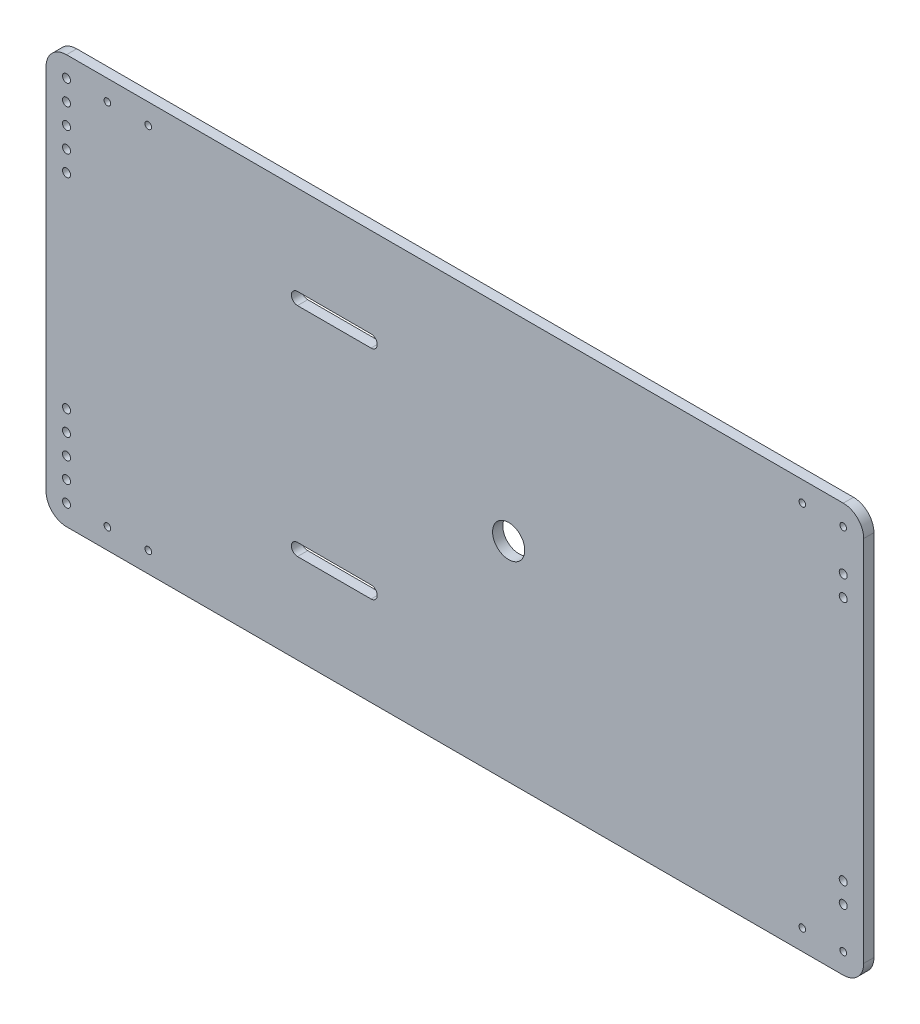
SolidWorks part; units mm, degrees
material "PC High Viscosity"
ref_plane "Front Plane" through (0, 0, 0) normal (0, 0, 1) x (1, 0, 0)
ref_plane "Top Plane" through (0, 0, 0) normal (0, 1, 0) x (1, 0, 0)
ref_plane "Right Plane" through (0, 0, 0) normal (1, 0, 0) x (0, 0, -1)
sketch "Sketch1" plane through (0, 0, 0) normal (0, 0, 1) x (1, 0, 0)
  line L1 (12.7, 0) -> (495.3, 0)
  line L2 (0, 12.7) -> (0, 241.3)
  line L3 (12.7, 254) -> (495.3, 254)
  line L4 (508, 12.7) -> (508, 241.3)
  arc A0 (495.3, 254) -> (508, 241.3) centre (495.3, 241.3) cw
  arc A1 (495.3, 0) -> (508, 12.7) centre (495.3, 12.7) ccw
  arc A2 (12.7, 0) -> (0, 12.7) centre (12.7, 12.7) cw
  arc A3 (0, 241.3) -> (12.7, 254) centre (12.7, 241.3) cw
  point P7 (508, 254)
  point P10 (508, 0)
  point P13 (0, 0)
  point P16 (0, 254)
  dimension "D3" = 12.7
  dimension "D1" = 508
  dimension "D2" = 254
extrude "Boss-Extrude1" add sketch "Sketch1" along normal blind 6.35
sketch "Sketch2" plane through (0, 0, 6.35) normal (0, 0, 1) x (1, 0, 0)
  line L10 (495.3, 254) -> (12.7, 254) construction
  line L11 (0, 241.3) -> (0, 12.7) construction
  line L12 (-20.2403, 127) -> (522.5431, 127) construction
  circle A6 centre (12.7, 190.5) radius 2.5
  circle A7 centre (12.7, 203.2) radius 2.5
  circle A8 centre (12.7, 215.9) radius 2.5
  circle A9 centre (12.7, 228.6) radius 2.5
  circle A10 centre (12.7, 241.3) radius 2.4892
  circle A11 centre (38.1, 241.3) radius 2.0701
  circle A12 centre (63.5, 241.3) radius 2.0701
  circle A13 centre (63.5, 12.7) radius 2.0701
  circle A14 centre (38.1, 12.7) radius 2.0701
  circle A15 centre (12.7, 63.5) radius 2.5
  circle A16 centre (12.7, 50.8) radius 2.5
  circle A17 centre (12.7, 38.1) radius 2.5
  circle A18 centre (12.7, 25.4) radius 2.5
  circle A19 centre (12.7, 12.7) radius 2.4892
  dimension "D2" = 12.7
  dimension "D3" = 5
  dimension "D4" = 4.1402
  dimension "D5" = 4.1402
  dimension "D6" = 4.9784
  dimension "D7" = 5
  dimension "D8" = 5
  dimension "D9" = 5
  dimension "D10" = 12.7
  dimension "D11" = 127
  dimension "D12" = 25.4
  dimension "D13" = 25.4
  dimension "D14" = 12.7
  dimension "D15" = 12.7
  dimension "D16" = 12.7
  dimension "D17" = 12.7
extrude "Cut-Extrude1" cut sketch "Sketch2" against normal through all
sketch "Sketch3" plane through (0, 0, 6.35) normal (0, 0, 1) x (1, 0, 0)
  line L8 (495.3, 254) -> (12.7, 254) construction
  line L11 (508, 12.7) -> (508, 241.3) construction
  line L12 (-50.4543, 127) -> (582.5907, 127) construction
  circle A0 centre (469.8795, 241.3) radius 2.0701
  circle A1 centre (495.2795, 241.3) radius 2.0701
  circle A4 centre (495.2795, 215.9) radius 2.4892
  circle A5 centre (495.2795, 203.2) radius 2.4892
  circle A16 centre (469.8795, 12.7) radius 2.0701
  circle A17 centre (495.2795, 12.7) radius 2.0701
  circle A18 centre (495.2795, 38.1) radius 2.4892
  circle A19 centre (495.2795, 50.8) radius 2.4892
  dimension "D1" = 4.1402
  dimension "D2" = 4.9784
  dimension "D3" = 12.7
  dimension "D4" = 12.7205
  dimension "D5" = 127
  dimension "D10" = 25.4
  dimension "D13" = 25.4
  dimension "D15" = 12.7
extrude "Cut-Extrude2" cut sketch "Sketch3" against normal through all
sketch "Sketch4" plane through (0, 0, 6.35) normal (0, 0, 1) x (1, 0, 0)
  line L0 (495.3, 254) -> (12.7, 254) construction
  line L1 (101.6, 178.054) -> (256.6, 178.054) construction
  line L2 (101.6, 178.054) -> (101.6, 76.054) construction
  line L3 (101.6, 76.054) -> (256.6, 76.054) construction
  line L4 (256.6, 178.054) -> (256.6, 76.054) construction
  line L6 (0, 241.3) -> (0, 12.7) construction
  line L7 (156.21, 194.564) -> (201.93, 194.564) construction
  line L8 (156.21, 198.374) -> (201.93, 198.374)
  line L9 (156.21, 190.754) -> (201.93, 190.754)
  line L10 (156.21, 59.544) -> (201.93, 59.544) construction
  line L11 (156.21, 63.354) -> (201.93, 63.354)
  line L12 (156.21, 55.734) -> (201.93, 55.734)
  arc A0 (156.21, 198.374) -> (156.21, 190.754) centre (156.21, 194.564) ccw
  arc A1 (201.93, 190.754) -> (201.93, 198.374) centre (201.93, 194.564) ccw
  arc A2 (156.21, 63.354) -> (156.21, 55.734) centre (156.21, 59.544) ccw
  arc A3 (201.93, 55.734) -> (201.93, 63.354) centre (201.93, 59.544) ccw
  point P10 (179.07, 194.564)
  point P15 (179.07, 59.544)
  dimension "D7" = 3.81
  dimension "D9" = 3.81
  dimension "D1" = 155
  dimension "D2" = 102
  dimension "D3" = 75.946
  dimension "D4" = 101.6
  dimension "D5" = 77.47
  dimension "D6" = 45.72
  dimension "D8" = 45.72
  dimension "D10" = 12.7
  dimension "D11" = 12.7
extrude "Cut-Extrude3" cut sketch "Sketch4" against normal through all
sketch "Sketch5" plane through (0, 0, 6.35) normal (0, 0, 1) x (1, 0, 0)
  line L0 (307.5263, 284.1622) -> (307.5263, -18.394) construction
  line L1 (508, 12.7) -> (508, 241.3) construction
  line L2 (12.7, 0) -> (495.3, 0) construction
  line L3 (0, 241.3) -> (0, 12.7) construction
  circle A0 centre (287.4065, 129.6573) radius 10
  dimension "D3" = 129.6573
  dimension "15mm" = 20
  dimension "D1" = 200.4737
  dimension "D2" = 302.5562
  dimension "D4" = 287.4065
extrude "Cut-Extrude4" cut sketch "Sketch5" against normal through all
